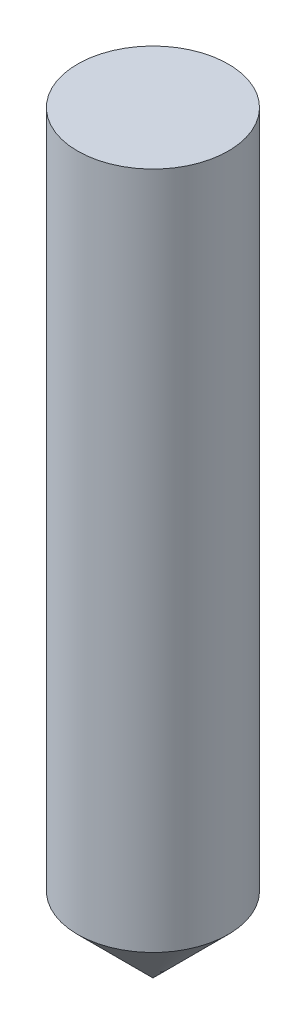
SolidWorks part; units mm, degrees
ref_plane "Front Plane" through (0, 0, 0) normal (0, 0, 1) x (1, 0, 0)
ref_plane "Top Plane" through (0, 0, 0) normal (0, 1, 0) x (1, 0, 0)
ref_plane "Right Plane" through (0, 0, 0) normal (1, 0, 0) x (0, 0, -1)
sketch "Sketch1" plane through (0, 0, 0) normal (0, 1, 0) x (1, 0, 0)
  circle A0 centre (0, 0) radius 5
extrude "Boss-Extrude2" add sketch "Sketch1" along normal blind 50 contours A0
chamfer "Chamfer2" distance 5 angle 45 1 edges at (0, 0, 5)
ref_axis "Axis1" through (0, 69.0236, 0) along (0, -1, 0)
ref_point "Point1"
